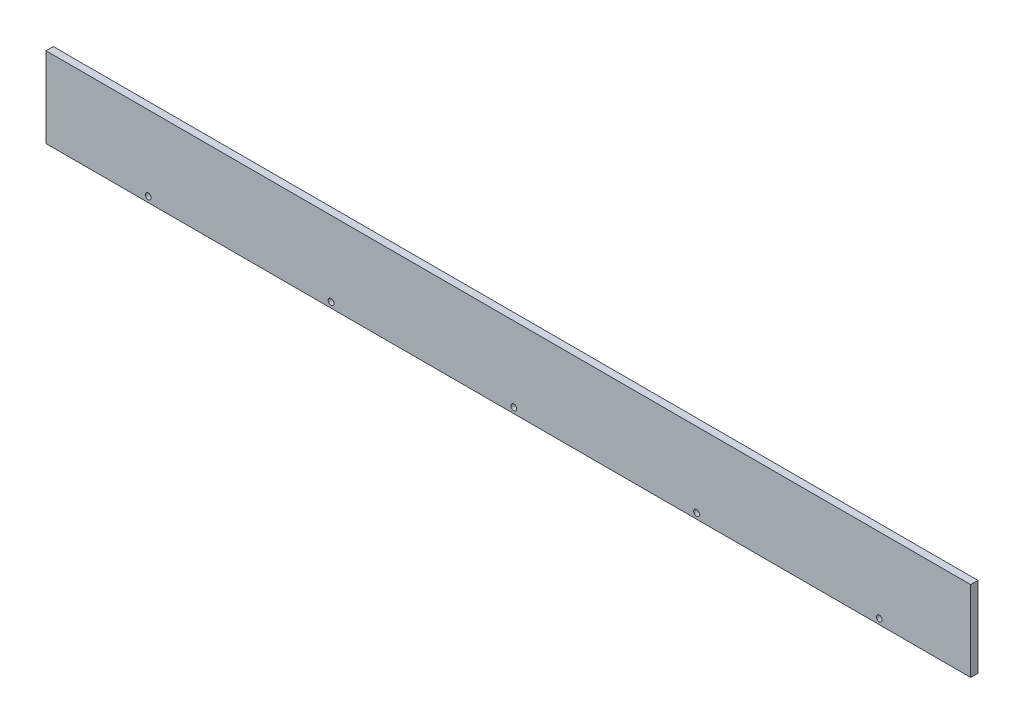
SolidWorks part; units mm, degrees
ref_plane "Front Plane" through (0, 0, 0) normal (0, 0, 1) x (1, 0, 0)
ref_plane "Top Plane" through (0, 0, 0) normal (0, 1, 0) x (1, 0, 0)
ref_plane "Right Plane" through (0, 0, 0) normal (1, 0, 0) x (0, 0, -1)
sketch "Sketch1" plane through (0, 0, 0) normal (0, 0, 1) x (1, 0, 0)
  line L1 (-253, -22) -> (253, -22)
  line L2 (-253, -22) -> (-253, 22)
  line L3 (-253, 22) -> (253, 22)
  line L4 (253, -22) -> (253, 22)
  line L5 (-253, -22) -> (253, 22) construction
  line L6 (-253, 22) -> (253, -22) construction
  circle A10 centre (203, -19) radius 1.6 construction
  circle A11 centre (103, -19) radius 1.6 construction
  circle A12 centre (3, -19) radius 1.6 construction
  circle A13 centre (-97, -19) radius 1.6 construction
  circle A14 centre (-197, -19) radius 1.6 construction
  circle A15 centre (203, -19) radius 1.6
  circle A16 centre (103, -19) radius 1.6
  circle A17 centre (3, -19) radius 1.6
  circle A18 centre (-97, -19) radius 1.6
  circle A19 centre (-197, -19) radius 1.6
  point P0 (0, 0)
  dimension "D1" = 506
  dimension "D2" = 44
extrude "Boss-Extrude1" add sketch "Sketch1" along normal blind 4
